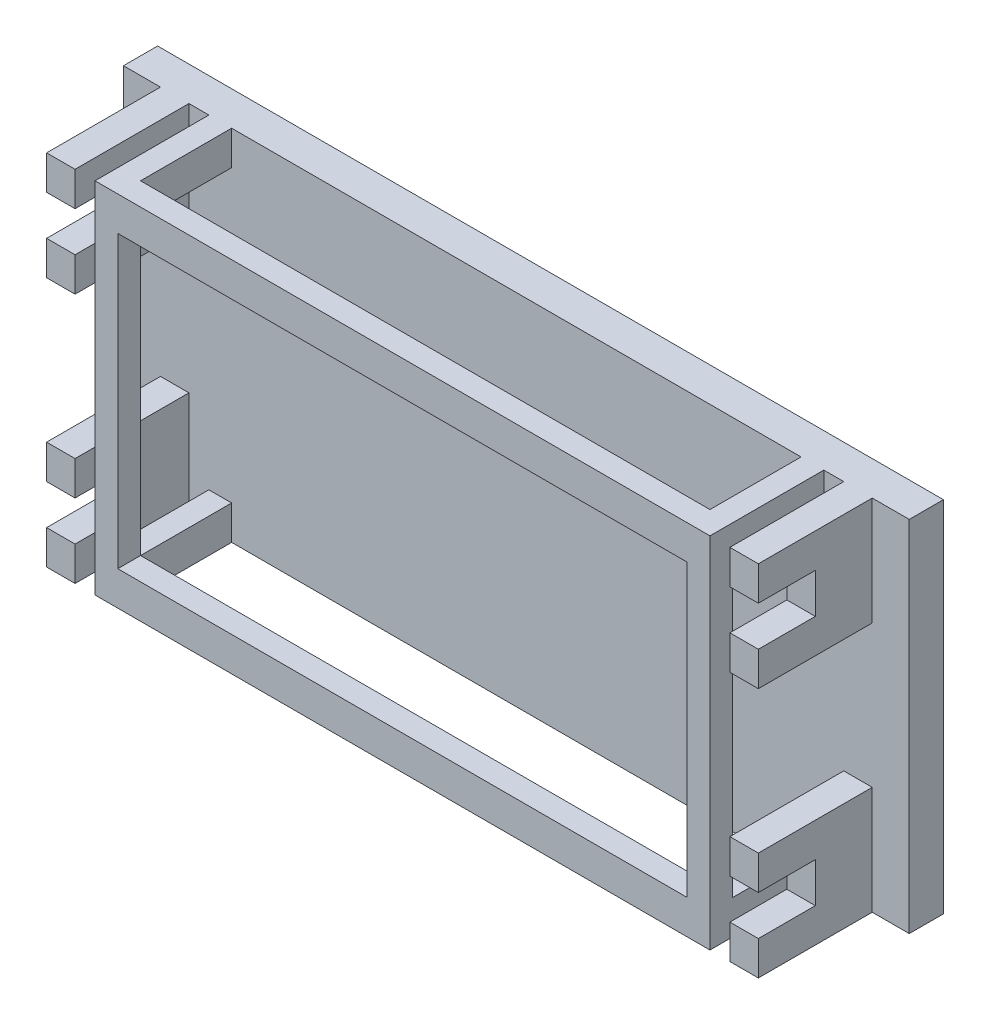
SolidWorks part; units mm, degrees
ref_plane "Plano frontal" through (0, 0, 0) normal (0, 0, 1) x (1, 0, 0)
ref_plane "Plano superior" through (0, 0, 0) normal (0, 1, 0) x (1, 0, 0)
ref_plane "Plano direito" through (0, 0, 0) normal (1, 0, 0) x (0, 0, -1)
sketch "Esboço1" plane through (0, 0, 0) normal (0, 0, 1) x (1, 0, 0)
  line L0 (0, -31.682) -> (0, -0.182)
  line L1 (0, -31.682) -> (-69, -31.682)
  line L3 (0, -0.182) -> (-69, -0.182)
  line L4 (-69, -31.682) -> (-69, -0.182)
  point P0 (0, 0)
  dimension "D1" = 31.5
  dimension "D2" = 69
extrude "Ressalto-extrusão1" add sketch "Esboço1" along normal blind 6
sketch "Esboço2" plane through (0, 0, 6) normal (0, 0, 1) x (1, 0, 0)
  line L0 (-69, -31.682) -> (0, -31.682) construction
  line L1 (-62.5, -31.682) -> (-57.5, -31.682)
  line L2 (-62.5, -31.682) -> (-62.5, -12.682)
  line L3 (-62.5, -12.682) -> (-57.5, -12.682)
  line L4 (-57.5, -31.682) -> (-57.5, -12.682)
  line L5 (-69, -0.182) -> (-69, -31.682) construction
  dimension "D1" = 19
  dimension "D2" = 5
  dimension "D3" = 6.5
extrude "Ressalto-extrusão2" add sketch "Esboço2" along normal blind 20
sketch "Esboço3" plane through (0, 0, 26) normal (0, 0, 1) x (1, 0, 0)
  line L0 (-57.5, -31.682) -> (-57.5, -12.682) construction
  line L1 (-57.5, -18.682) -> (-62.5, -18.682)
  line L2 (-57.5, -18.682) -> (-57.5, -25.682)
  line L3 (-57.5, -25.682) -> (-62.5, -25.682)
  line L4 (-62.5, -18.682) -> (-62.5, -25.682)
  line L5 (-62.5, -12.682) -> (-62.5, -31.682) construction
  line L6 (-57.5, -12.682) -> (-62.5, -12.682) construction
  line L7 (-62.5, -31.682) -> (-57.5, -31.682) construction
  dimension "D1" = 6
  dimension "D2" = 6
extrude "Corte-extrusão1" cut sketch "Esboço3" against normal blind 10
sketch "Esboço4" plane through (0, 0, 6) normal (0, 0, 1) x (1, 0, 0)
  line L0 (-57.5, -31.682) -> (0, -31.682) construction
  line L1 (-54, -31.682) -> (-50, -31.682)
  line L2 (-54, -31.682) -> (-54, -0.182)
  line L3 (-54, -0.182) -> (-50, -0.182)
  line L4 (-50, -31.682) -> (-50, -0.182)
  line L5 (0, -0.182) -> (-69, -0.182) construction
  line L6 (-57.5, -31.682) -> (-57.5, -12.682) construction
  dimension "D1" = 3.5
  dimension "D2" = 4
extrude "Ressalto-extrusão3" add sketch "Esboço4" along normal blind 20
sketch "Esboço5" plane through (-50, 0, 0) normal (1, 0, 0) x (0, 0, -1)
  line L1 (-22, -25.682) -> (-6, -25.682)
  line L2 (-22, -25.682) -> (-22, -6.182)
  line L5 (-26, -31.682) -> (-6, -31.682) construction
  line L6 (-22, -6.182) -> (-22, -0.182)
  line L7 (-26, -0.182) -> (-6, -0.182) construction
  line L8 (-22, -0.182) -> (-6, -0.182)
  line L10 (-26, -31.682) -> (-26, -0.182) construction
  line L12 (-6, -31.682) -> (-6, -0.182) construction
  line L13 (-6, -25.682) -> (-6, -0.182)
  dimension "D1" = 4
  dimension "D2" = 6
extrude "Corte-extrusão2" cut sketch "Esboço5" against normal up to surface (4 mm away) up to face at (-54, -15.932, 16)
sketch "Esboço6" plane through (-50, 0, 0) normal (1, 0, 0) x (0, 0, -1)
  line L1 (-26, -31.682) -> (-22, -31.682)
  line L2 (-26, -31.682) -> (-26, -25.682)
  line L3 (-26, -25.682) -> (-22, -25.682)
  line L4 (-22, -31.682) -> (-22, -25.682)
extrude "Ressalto-extrusão4" add sketch "Esboço6" along normal up to surface (50 mm away) up to face at (0, -15.932, 3)
ref_plane "Plano2" through (0, -0.182, 0) normal (0, 1, 0) x (1, 0, 0)
mirror "Espelhar10" about plane through (0, -0.182, 0) normal (0, 1, 0) of bodies 110 103
ref_plane "Plano1" through (0, 0, 0) normal (1, 0, 0) x (0, 0, -1)
mirror "Espelhar11" about plane through (0, 0, 0) normal (1, 0, 0) of bodies 106
